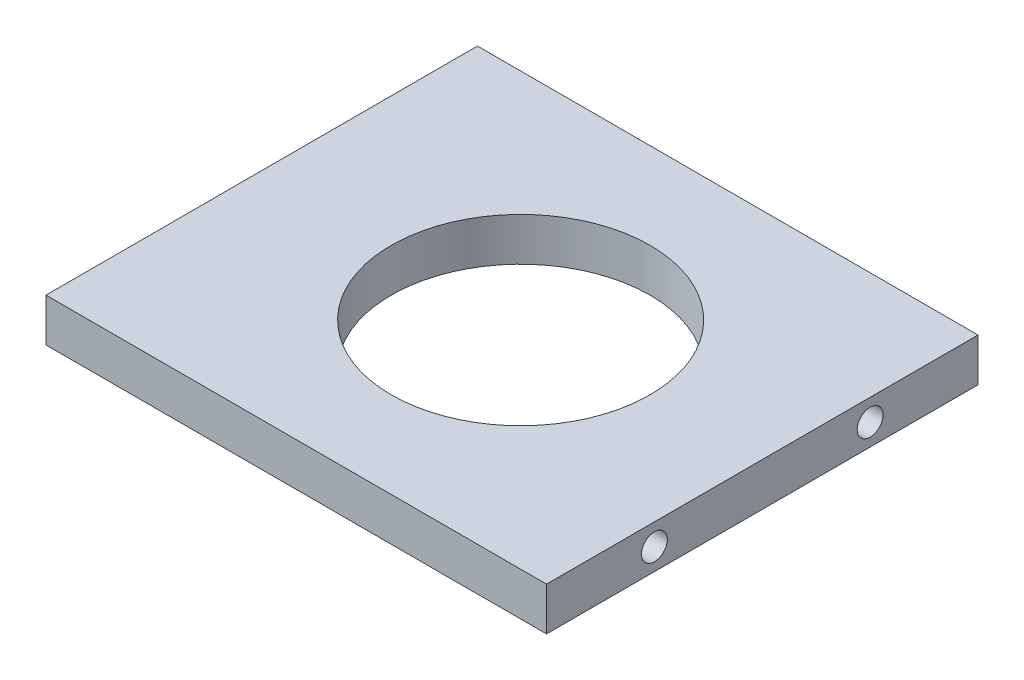
SolidWorks part; units mm, degrees
ref_plane "Plan de face" through (0, 0, 0) normal (0, 0, 1) x (1, 0, 0)
ref_plane "Plan de dessus" through (0, 0, 0) normal (0, 1, 0) x (1, 0, 0)
ref_plane "Plan de droite" through (0, 0, 0) normal (1, 0, 0) x (0, 0, -1)
sketch "Esquisse1" plane through (0, 0, 0) normal (0, 0, 1) x (1, 0, 0)
  line L0 (-5.5, -47.5) -> (52.5, -47.5) construction
  line L5 (-5.5, -45) -> (52.5, -45)
  line L6 (-5.5, -45) -> (-5.5, -50)
  line L7 (-5.5, -50) -> (52.5, -50)
  line L8 (52.5, -45) -> (52.5, -50)
  line L9 (23.5, -45) -> (23.5, -50) construction
  dimension "D1" = 5
  dimension "D2" = 58
extrude "Boss.-Extru.1" add sketch "Esquisse1" along normal blind 50 contours L5 | L7 L8 L5 L6
sketch "Esquisse2" plane through (0, -45, 0) normal (0, 1, 0) x (-1, 0, 0)
  line L0 (5.5, 50) -> (-52.5, 50) construction
  line L7 (-52.5, 50) -> (-52.5, 0) construction
  circle A0 centre (-24.5, 25) radius 15
  dimension "D10" = 28
  dimension "D11" = 25
extrude "Enlèv. mat.-Extru.1" cut sketch "Esquisse2" against normal through all
sketch "Esquisse3" plane through (-5.5, 0, 0) normal (-1, 0, 0) x (0, 0, 1)
  line L0 (50, -50) -> (0, -50) construction
  line L1 (0, -45) -> (0, -50) construction
  line L2 (50, -45) -> (50, -50) construction
  circle A0 centre (12.5, -47.5) radius 1.5
  circle A1 centre (37.5, -47.5) radius 1.5
  dimension "D1" = 2.5
  dimension "D2" = 2.5
  dimension "D3" = 12.5
  dimension "D4" = 12.5
extrude "Enlèv. mat.-Extru.2" cut sketch "Esquisse3" against normal blind 10
sketch "Esquisse4" plane through (52.5, 0, 0) normal (1, 0, 0) x (0, 0, -1)
  line L0 (-50, -50) -> (0, -50) construction
  line L1 (-50, -45) -> (-50, -50) construction
  line L2 (0, -45) -> (0, -50) construction
  circle A0 centre (-37.5, -47.5) radius 1.5
  circle A1 centre (-12.5, -47.5) radius 1.5
  dimension "D1" = 2.5
  dimension "D2" = 2.5
  dimension "D3" = 12.5
  dimension "D4" = 12.5
extrude "Enlèv. mat.-Extru.3" cut sketch "Esquisse4" against normal blind 10
